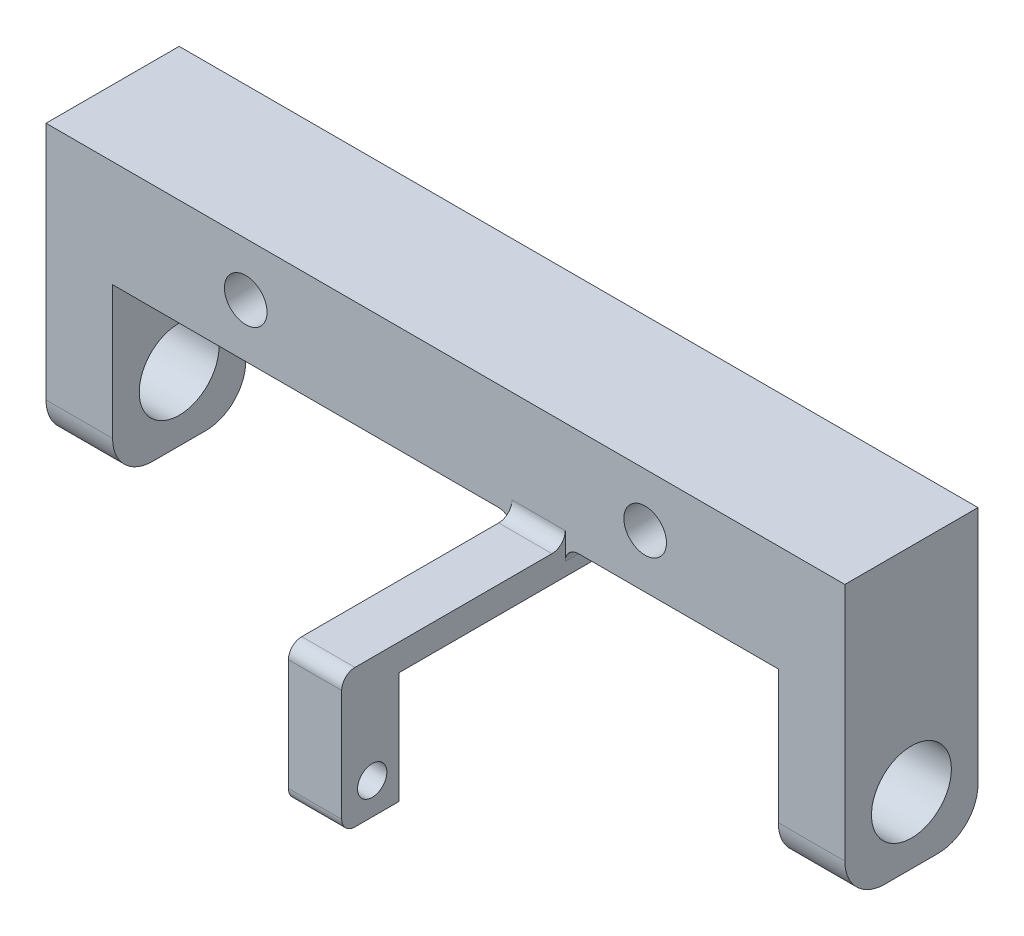
SolidWorks part; units mm, degrees
ref_plane "前视基准面" through (0, 0, 0) normal (0, 0, 1) x (1, 0, 0)
ref_plane "上视基准面" through (0, 0, 0) normal (0, 1, 0) x (1, 0, 0)
ref_plane "右视基准面" through (0, 0, 0) normal (1, 0, 0) x (0, 0, -1)
sketch "草图1" plane through (0, 0, 0) normal (0, 1, 0) x (1, 0, 0)
  line L1 (30, -5) -> (-30, -5)
  line L2 (30, -5) -> (30, 5)
  line L3 (30, 5) -> (-30, 5)
  line L4 (-30, -5) -> (-30, 5)
  line L5 (30, -5) -> (-30, 5) construction
  line L6 (30, 5) -> (-30, -5) construction
  point P0 (0, 0)
extrude "凸台-拉伸1" add sketch "草图1" along normal blind 8
sketch "草图2" plane through (30, 0, 0) normal (1, 0, 0) x (0, 0, -1)
  line L1 (-5, 8) -> (5, 8)
  line L2 (-5, 8) -> (-5, -13)
  line L3 (-5, -13) -> (5, -13)
  line L4 (5, 8) -> (5, -13)
  circle A0 centre (0, -8) radius 3
  point P7 (0, 0)
extrude "凸台-拉伸2" add sketch "草图2" against normal blind 5
mirror "镜向1" about plane through (0, 0, 0) normal (1, 0, 0) of "凸台-拉伸2"
fillet "圆角1" radius 3 4 edges at (-27.5, -13, -5) (-27.5, -13, 5) (27.5, -13, -5) (27.5, -13, 5)
ref_plane "基准面1" through (5, 0, 0) normal (-1, 0, 0) x (0, 0, 1)
sketch "草图3" plane through (5, 0, 0) normal (-1, 0, 0) x (0, 0, 1)
  line L0 (-8.5, -8) -> (-8.5, -2) construction
  line L1 (-6.5, -2) -> (17.5, -2)
  line L2 (-8.5, -8) -> (-6.5, -8) construction
  line L3 (-6.5, -8) -> (-6.5, -2)
  line L4 (-6.5, -8) -> (-6.5, -10.3764)
  line L5 (-6.5, -10.3764) -> (-10.8679, -10.3764)
  line L6 (-10.8679, -10.3764) -> (-10.8679, 0)
  line L7 (-10.8679, 0) -> (21.7929, 0)
  line L8 (19.5, -8) -> (17.5, -8) construction
  line L9 (17.5, -8) -> (17.5, -2)
  line L10 (17.5, -8) -> (17.5, -10.3764)
  line L11 (17.5, -10.3764) -> (21.7929, -10.3764)
  line L12 (21.7929, -10.3764) -> (21.7929, 0)
  circle A0 centre (0, -8) radius 3 construction
  circle A1 centre (0, -8) radius 3 construction
  circle A2 centre (-8.5, -8) radius 1.1
  circle A3 centre (19.5, -8) radius 1.1
extrude "凸台-拉伸3" add sketch "草图3" against normal blind 4
fillet "圆角3" radius 1 6 edges at (7, -10.3764, -10.8679) (7, 0, -10.8679) (7, -10.3764, 21.7929) (7, 0, 21.7929) (7, 0, -5) (7, 0, 5)
fillet "圆角4" radius 1 2 edges at (9, 0, 0) (5, 0, 0)
sketch "草图4" plane through (0, 0, 5) normal (0, 0, 1) x (1, 0, 0)
  circle A0 centre (-15, 4) radius 1.6
  circle A1 centre (15, 4) radius 1.6
extrude "切除-拉伸1" cut sketch "草图4" against normal through all both and the other way through all
